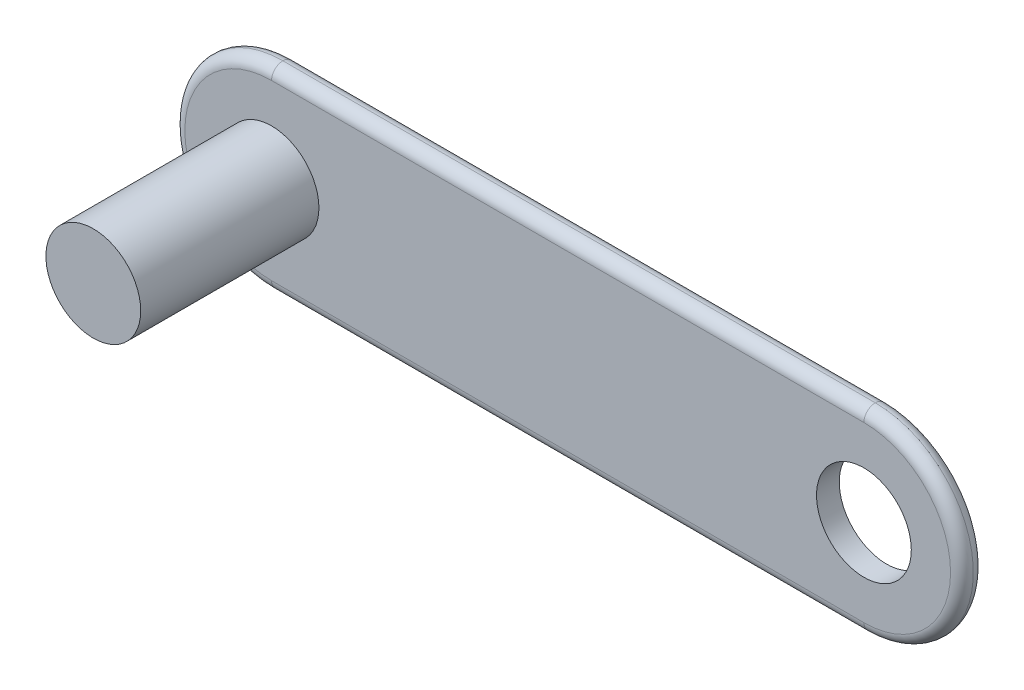
SolidWorks part; units mm, degrees
ref_plane "Front Plane" through (0, 0, 0) normal (0, 0, 1) x (1, 0, 0)
ref_plane "Top Plane" through (0, 0, 0) normal (0, 1, 0) x (1, 0, 0)
ref_plane "Right Plane" through (0, 0, 0) normal (1, 0, 0) x (0, 0, -1)
sketch "Sketch2" plane through (0, 0, 0) normal (0, 0, 1) x (1, 0, 0)
  line L0 (0, 0) -> (79.3592, 0) construction
  line L1 (0, 13.1353) -> (79.3592, 13.1353)
  line L2 (0, -13.1353) -> (79.3592, -13.1353)
  arc A0 (0, 13.1353) -> (0, -13.1353) centre (0, 0) ccw
  arc A1 (79.3592, -13.1353) -> (79.3592, 13.1353) centre (79.3592, 0) ccw
  point P3 (39.6796, 0)
extrude "Boss-Extrude1" add sketch "Sketch2" along normal mid plane 3.048
fillet "Fillet1" radius 1.524 8 edges at (92.4945, 0, -1.524) (39.6796, -13.1353, -1.524) (-13.1353, 0, -1.524) (92.4945, 0, 1.524) (39.6796, -13.1353, 1.524) (-13.1353, 0, 1.524) (39.6796, 13.1353, -1.524) (39.6796, 13.1353, 1.524)
sketch "Sketch3" plane through (0, 0, 0) normal (0, 0, 1) x (1, 0, 0)
  circle A0 centre (0, 0) radius 6.35
  dimension "D1" = 12.7
extrude "Boss-Extrude3" add sketch "Sketch3" along normal blind 25.4
sketch "Sketch5" plane through (0, 0, 0) normal (0, 0, 1) x (1, 0, 0)
  circle A0 centre (79.3592, 0) radius 6.35
  point P3 (0, 0)
  dimension "D1" = 12.7
extrude "Cut-Extrude4" cut sketch "Sketch5" against normal through all both and the other way through all
